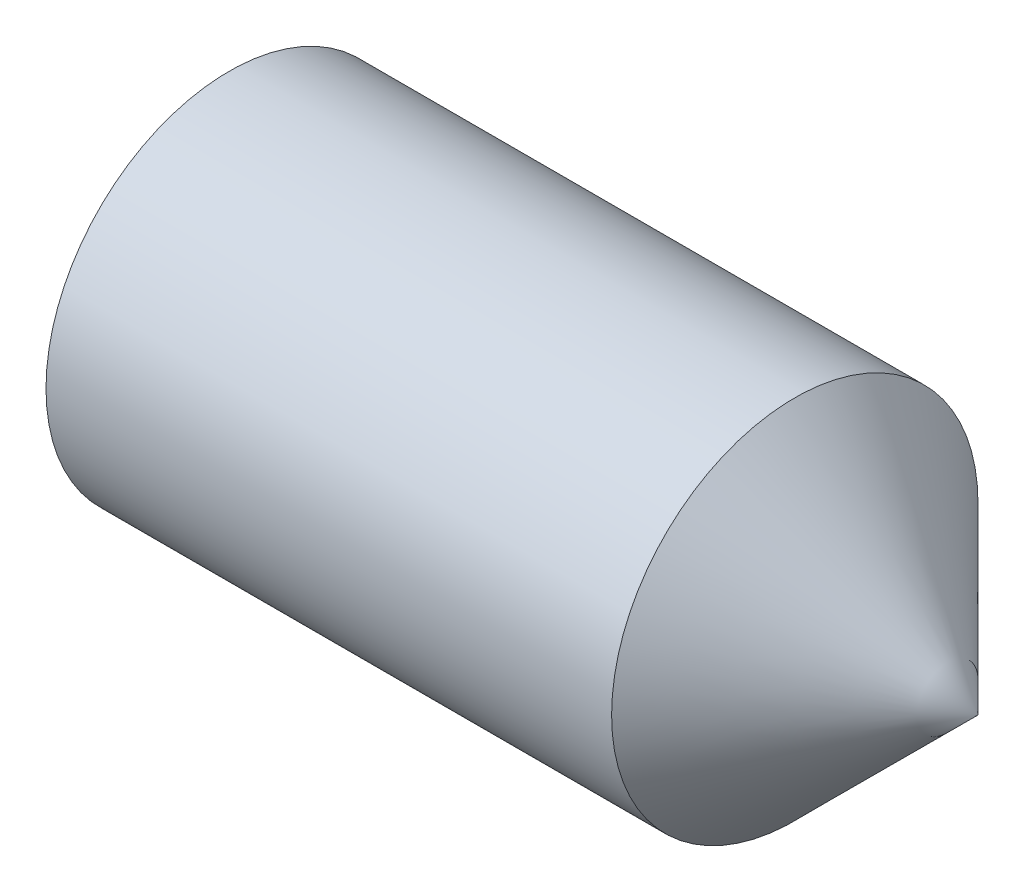
SolidWorks part; units mm, degrees
revolve "BaseBody" add sketch "BodySke" angle 360 about L5 other way angle 60
sketch "BodySke" plane through (0, 0, 0) normal (0, 0, 1) x (1, 0, 0)
  line L0 (0, 0) -> (0, 10.352)
  line L1 (0, 10.352) -> (0.9515, 12)
  line L2 (0.9515, 12) -> (38, 12)
  line L3 (38, 12) -> (50, 0)
  line L4 (50, 0) -> (0, 0)
  line L5 (-12.7, 0) -> (88.9, 0) construction
  line L6 (38, -12) -> (50, 0) construction
  line L7 (1.5, 15.875) -> (1.5, -3.175) construction
  line L8 (0, -10.352) -> (0.9515, -12) construction
  dimension "Cone_ang" = 90
  dimension "Length" = 50
  dimension "Diameter" = 24
cosmetic thread "ThreadCosmetic" [suppressed] parameters "Thread_minor"=20.704
ref_plane "Plane1" through (0, 0, 0) normal (0, 0, 1) x (1, 0, 0)
ref_plane "Plane2" through (0, 0, 0) normal (0, 1, 0) x (1, 0, 0)
ref_plane "Plane3" through (0, 0, 0) normal (1, 0, 0) x (0, 0, -1)
sketch "Sketch2" plane through (0, 0, 0) normal (-1, 0, 0) x (0, 0, 1)
  line L0 (3.4641, 6) -> (-3.4641, 6)
  line L1 (-3.4641, 6) -> (-6.9282, 0)
  line L2 (3.4641, 6) -> (6.9282, 0)
  line L3 (3.4641, -6) -> (6.9282, 0)
  line L4 (3.4641, -6) -> (-3.4641, -6)
  line L5 (-3.4641, -6) -> (-6.9282, 0)
  dimension "D2" = 6
  dimension "D3" = 6
extrude "Hex" cut sketch "Sketch2" against normal blind 15
sketch "ThdSchSke" plane through (0, 0, 0) normal (0, 0, 1) x (1, 0, 0)
  line L0 (0.9515, -10.352) -> (-0.2025, -12)
  line L1 (0.9515, -10.352) -> (2.1054, -12)
  line L2 (2.1054, -12) -> (2.1054, -15)
  line L3 (-3.175, 0) -> (5.1513, 0) construction
  line L4 (0.9515, 12) -> (0.9515, -12) construction
  line L5 (2.1054, -15) -> (-0.2025, -15)
  line L6 (-0.2025, -15) -> (-0.2025, -12)
  dimension "Thread_minor" = 20.704
  dimension "Diameter" = 24
revolve "ThreadSchematic" [suppressed] cut sketch "ThdSchSke" angle 360 about L3
pattern_linear "ThdSchPat" [suppressed]
equation "\"D2@Sketch2\" = \"Hex_size@Sketch2\" / 2"
equation "\"D3@Sketch2\" = \"Hex_size@Sketch2\" / 2"
equation "\"Thread_minor@ThreadCosmetic\" = \"Minor_dia@BodySke\""
equation "\"Thread_minor@ThdSchSke\" = \"Thread_minor@ThreadCosmetic\""
equation "\"Diameter@ThdSchSke\" = \"Diameter@BodySke\""
equation "\"Overcut@ThdSchSke\" = \"Diameter@BodySke\" * 1.25"
equation "\"Num_threads@ThdSchPat\" = int( (\"Length@BodySke\" - ( ( ( \"Diameter@BodySke\" - \"Minor_dia@BodySke\" ) * 0.5 ) / tan( \"Drive_ch_ang@BodySke\" * 0.017453292 ) ) - ( ( \"Diameter@BodySke\" * 0.5 ) / tan( \"Cone_ang@BodySke\" * 0.008726646 ) ) ) / \"Advance@BodySke\" + 0.999 )  + 1"
equation "\"Advance@ThdSchPat\" = (\"Length@BodySke\" - ( ( ( \"Diameter@BodySke\" - \"Minor_dia@BodySke\" ) * 0.5 ) / tan( \"Drive_ch_ang@BodySke\" * 0.017453292 ) ) - ( ( \"Diameter@BodySke\" * 0.5 ) / tan( \"Cone_ang@BodySke\" * 0.008726646 ) ) ) /  (\"Num_threads@ThdSchPat\" - 1) 'relax it"
equation "' \"Num_threads@ThdSchPat\" = \"Num_threads@ThdSchPat\" - sgn( \"Num_threads@ThdSchPat\" - 1) '---chamfered tips only---"
